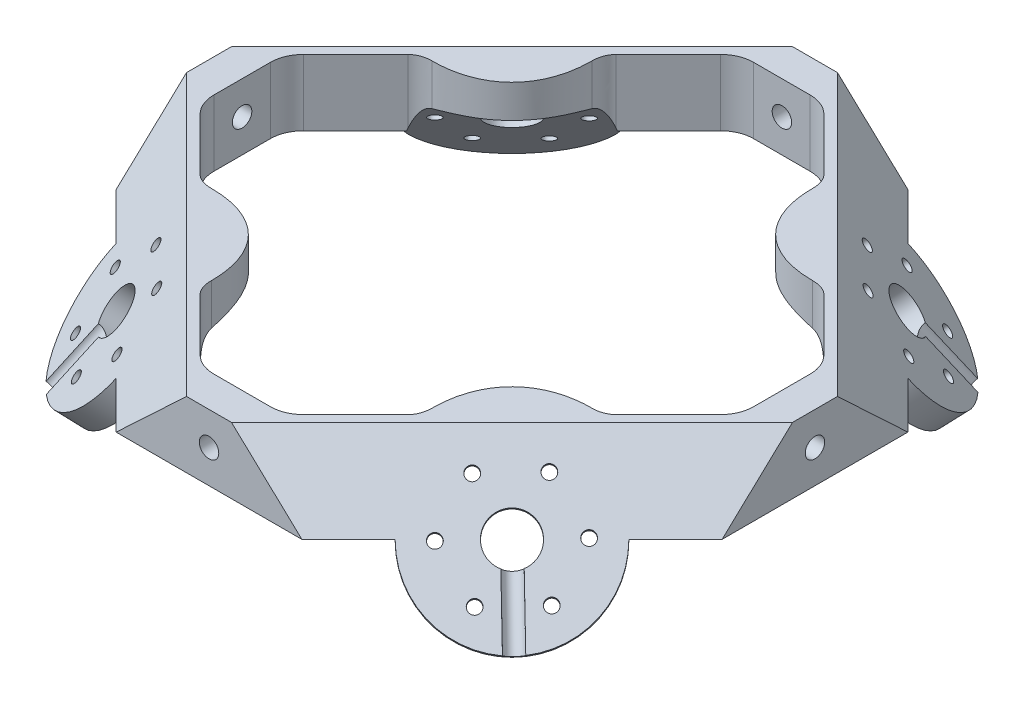
SolidWorks part; units mm, degrees
ref_plane "Front Plane" through (0, 0, 0) normal (0, 0, 1) x (1, 0, 0)
ref_plane "Top Plane" through (0, 0, 0) normal (0, 1, 0) x (1, 0, 0)
ref_plane "Right Plane" through (0, 0, 0) normal (1, 0, 0) x (0, 0, -1)
sketch "Sketch2" plane through (0, 0, 0) normal (0, 1, 0) x (1, 0, 0)
  line L1 (-45.825, -45.825) -> (45.825, -45.825)
  line L2 (-45.825, -45.825) -> (-45.825, 45.825)
  line L3 (-45.825, 45.825) -> (45.825, 45.825)
  line L4 (45.825, -45.825) -> (45.825, 45.825)
  line L5 (-45.825, -45.825) -> (45.825, 45.825) construction
  line L6 (-45.825, 45.825) -> (45.825, -45.825) construction
  circle A0 centre (0, 0) radius 3.175
  point P0 (0, 0)
  dimension "D2" = 6.35
  dimension "D1" = 91.65
extrude "Boss-Extrude2" add sketch "Sketch2" along normal blind 10
sketch "Sketch22" plane through (0, 10, 0) normal (0, 1, 0) x (1, 0, 0)
  circle A0 centre (0, 0) radius 3.9133
ref_axis "Axis4" through (0, 10, 0) along (0, 1, 0)
sketch "Sketch3" plane through (0, 10, 0) normal (0, 1, 0) x (1, 0, 0)
  line L0 (-45.825, -3.3986) -> (-3.3986, -45.825)
  line L1 (-45.825, 45.825) -> (-45.825, -45.825) construction
  line L2 (-45.825, -45.825) -> (45.825, -45.825) construction
  dimension "D1" = 45
  dimension "D2" = 30
ref_plane "Plane1" through (-19.0964, 20.3508, 19.0964) normal (-0.5647, 0.6018, 0.5647) x (0.7071, 0, 0.7071)
sketch "Sketch4" plane through (-19.0964, 20.3508, 19.0964) normal (-0.5647, 0.6018, 0.5647) x (0.7071, 0, 0.7071)
  line L0 (-30, -12.9606) -> (30, -12.9606) construction
  line L1 (30, -12.9606) -> (-30, -12.9606)
  line L2 (30, -12.9606) -> (30, -39.0014)
  line L3 (30, -39.0014) -> (-30, -39.0014)
  line L4 (-30, -12.9606) -> (-30, -39.0014)
extrude "Cut-Extrude1" cut sketch "Sketch4" along normal through all
sketch "Sketch5" plane through (-19.0964, 20.3508, 19.0964) normal (-0.5647, 0.6018, 0.5647) x (0.8253, 0.4118, 0.3864)
  line L3 (-32.3872, -10.2496) -> (6.1082, -33.4167) construction
  circle A0 centre (-13.1395, -21.8331) radius 12.5
  dimension "D1" = 25
extrude "Cut-Extrude2" cut sketch "Sketch5" against normal up to next from offset 4 offset against normal yes
sketch "Sketch6" plane through (-16.8376, 17.9436, 16.8376) normal (0.5647, -0.6018, -0.5647) x (0.8253, 0.4118, 0.3864)
  circle A0 centre (-13.1395, 21.8331) radius 12.5
  arc A1 (-21.9793, 12.9952) -> (-1.1912, 25.5058) centre (-13.1395, 21.8331) ccw construction
extrude "Boss-Extrude3" add sketch "Sketch6" against normal up to surface (4 mm away) up to face at (-27.276, 5, 27.276)
sketch "Sketch7" plane through (-16.8376, 17.9436, 16.8376) normal (0.5647, -0.6018, -0.5647) x (0.8253, 0.4118, 0.3864)
  line L1 (-13.1395, 13.5831) -> (-5.9948, 17.7081) construction
  line L2 (-5.9948, 17.7081) -> (-5.9948, 25.9581) construction
  line L3 (-5.9948, 25.9581) -> (-13.1395, 30.0831) construction
  line L4 (-13.1395, 30.0831) -> (-20.2842, 25.9581) construction
  line L5 (-20.2842, 25.9581) -> (-20.2842, 17.7081) construction
  line L6 (-20.2842, 17.7081) -> (-13.1395, 13.5831) construction
  circle A0 centre (-13.1395, 21.8331) radius 7.1447 construction
  circle A2 centre (-13.1395, 30.0831) radius 0.9
  circle A3 centre (-20.2842, 25.9581) radius 0.9
  circle A4 centre (-20.2842, 17.7081) radius 0.9
  circle A5 centre (-13.1395, 13.5831) radius 0.9
  circle A6 centre (-5.9948, 17.7081) radius 0.9
  circle A7 centre (-5.9948, 25.9581) radius 0.9
  circle A8 centre (-13.1395, 21.8331) radius 3.375
  arc A9 (-21.9793, 12.9952) -> (-1.1912, 25.5058) centre (-13.1395, 21.8331) ccw construction
  dimension "D2" = 1.8
  dimension "D3" = 6.75
  dimension "D1" = 16.5
extrude "Cut-Extrude3" cut sketch "Sketch7" against normal through all
ref_axis "Axis2" through (-29.4641, -6.1526, 35.4802) along (0.5647, -0.6018, -0.5647)
ref_axis "Axis3" through (-35.3605, -6.2723, 29.7113) along (0.5647, -0.6018, -0.5647)
ref_plane "Plane2" through (-13.4614, -26.0492, 14.2989) normal (-0.4126, -0.7985, 0.4383) x (0.2193, 0.3799, 0.8986)
sketch "Sketch17" plane through (-13.4614, -26.0492, 14.2989) normal (-0.4126, -0.7985, 0.4383) x (0.2193, 0.3799, 0.8986)
  line L0 (30.2204, 19.367) -> (10.456, 34.6728) construction
  circle A0 centre (20.3382, 27.0199) radius 1.25
  dimension "D1" = 2.5
extrude "Cut-Extrude8" cut sketch "Sketch17" against normal up to next and the other way through all
pattern_circular "CirPattern3" count 4 over 360 about axis through (0, 10, 0) along (0, 1, 0) of "Cut-Extrude8", "Cut-Extrude3", "Boss-Extrude3", "Cut-Extrude2", "Cut-Extrude1"
sketch "Sketch18" plane through (0, 0, 0) normal (0, -1, 0) x (1, 0, 0)
  line L0 (-14.0555, -45.825) -> (-21.1014, -38.7791) construction
  line L1 (-13.7845, -33.3905) -> (-6.35, -40.825)
  line L2 (-40.825, -6.35) -> (-40.825, 6.35)
  line L3 (-6.35, 40.825) -> (6.35, 40.825)
  line L4 (40.825, -6.35) -> (33.3905, -13.7845)
  line L5 (40.825, 6.35) -> (33.3905, 13.7845)
  line L6 (-45.825, -14.0555) -> (-45.825, 14.0555) construction
  line L7 (-6.35, -40.825) -> (6.35, -40.825)
  line L8 (13.7845, 33.3905) -> (6.35, 40.825)
  line L9 (-13.7845, 33.3905) -> (-6.35, 40.825)
  line L11 (40.825, -6.35) -> (40.825, 6.35)
  line L12 (14.0555, -45.825) -> (-14.0555, -45.825) construction
  line L13 (13.7845, -33.3905) -> (6.35, -40.825)
  line L14 (0, 0) -> (0, -40.825) construction
  line L20 (-40.825, 6.35) -> (-33.3905, 13.7845)
  line L21 (-40.825, -6.35) -> (-33.3905, -13.7845)
  line L22 (40.825, 0) -> (-40.825, 0) construction
  spline S0 degree 3 poles (651.7831, 1840.4478) (-301.2202, -130.8658) (-38.05, -89.2162) (-11.3299, -28.2857) (-10.7128, -26.1815) (-10.3137, -23.1157) (-10.2685, -22.1086) (-10.3687, -20.1466) (-10.5143, -19.1914) (-11.0109, -17.3644) (-11.3626, -16.4925) (-12.274, -14.8783) (-12.8342, -14.1368) (-14.1368, -12.8342) (-14.8783, -12.274) (-16.4925, -11.3626) (-17.3644, -11.0109) (-19.1914, -10.5143) (-20.1466, -10.3687) (-22.1086, -10.2685) (-23.1157, -10.3137) (-26.1815, -10.7128) (-28.2857, -11.3299) (-89.2167, -38.0502) (-130.8665, -301.225) (1840.5017, 651.8091) knots -3.40686 -3.40686 -3.40686 -3.40686 0.125 0.125 0.25 0.25 0.3125 0.3125 0.375 0.375 0.4375 0.4375 0.5 0.5 0.5625 0.5625 0.625 0.625 0.6875 0.6875 0.75 0.75 0.875 0.875 4.406893 4.406893 4.406893 4.406893 only from (-15.8109, -36.4636) to (-36.4636, -15.8109)
  spline S1 degree 3 poles (-13.7845, -33.3905) (-13.205, -32.3951) (-12.6888, -31.3843) (-11.3299, -28.2857) (-10.7128, -26.1815) (-10.3137, -23.1157) (-10.2685, -22.1086) (-10.3687, -20.1466) (-10.5143, -19.1914) (-11.0109, -17.3644) (-11.3626, -16.4925) (-12.274, -14.8783) (-12.8342, -14.1368) (-14.1368, -12.8342) (-14.8783, -12.274) (-16.4925, -11.3626) (-17.3644, -11.0109) (-19.1914, -10.5143) (-20.1466, -10.3687) (-22.1086, -10.2685) (-23.1157, -10.3137) (-26.1815, -10.7128) (-28.2857, -11.3299) (-31.3843, -12.6888) (-32.3951, -13.205) (-33.3905, -13.7845) knots 0.064029 0.064029 0.064029 0.064029 0.125 0.125 0.25 0.25 0.3125 0.3125 0.375 0.375 0.4375 0.4375 0.5 0.5 0.5625 0.5625 0.625 0.625 0.6875 0.6875 0.75 0.75 0.875 0.875 0.935971 0.935971 0.935971 0.935971
  spline S2 degree 3 poles (1840.4478, -651.7831) (-130.8658, 301.2202) (-89.2162, 38.05) (-28.2857, 11.3299) (-26.1815, 10.7128) (-23.1157, 10.3137) (-22.1086, 10.2685) (-20.1466, 10.3687) (-19.1914, 10.5143) (-17.3644, 11.0109) (-16.4925, 11.3626) (-14.8783, 12.274) (-14.1368, 12.8342) (-12.8342, 14.1368) (-12.274, 14.8783) (-11.3626, 16.4925) (-11.0109, 17.3644) (-10.5143, 19.1914) (-10.3687, 20.1466) (-10.2685, 22.1086) (-10.3137, 23.1157) (-10.7128, 26.1815) (-11.3299, 28.2857) (-38.0502, 89.2167) (-301.225, 130.8665) (651.8091, -1840.5017) knots -3.40686 -3.40686 -3.40686 -3.40686 0.125 0.125 0.25 0.25 0.3125 0.3125 0.375 0.375 0.4375 0.4375 0.5 0.5 0.5625 0.5625 0.625 0.625 0.6875 0.6875 0.75 0.75 0.875 0.875 4.406893 4.406893 4.406893 4.406893 only from (-36.4636, 15.8109) to (-15.8109, 36.4636)
  spline S3 degree 3 poles (-33.3905, 13.7845) (-32.3951, 13.205) (-31.3843, 12.6888) (-28.2857, 11.3299) (-26.1815, 10.7128) (-23.1157, 10.3137) (-22.1086, 10.2685) (-20.1466, 10.3687) (-19.1914, 10.5143) (-17.3644, 11.0109) (-16.4925, 11.3626) (-14.8783, 12.274) (-14.1368, 12.8342) (-12.8342, 14.1368) (-12.274, 14.8783) (-11.3626, 16.4925) (-11.0109, 17.3644) (-10.5143, 19.1914) (-10.3687, 20.1466) (-10.2685, 22.1086) (-10.3137, 23.1157) (-10.7128, 26.1815) (-11.3299, 28.2857) (-12.6888, 31.3843) (-13.205, 32.3951) (-13.7845, 33.3905) knots 0.064029 0.064029 0.064029 0.064029 0.125 0.125 0.25 0.25 0.3125 0.3125 0.375 0.375 0.4375 0.4375 0.5 0.5 0.5625 0.5625 0.625 0.625 0.6875 0.6875 0.75 0.75 0.875 0.875 0.935971 0.935971 0.935971 0.935971
  spline S4 degree 3 poles (33.3905, 13.7845) (32.3951, 13.205) (31.3843, 12.6888) (28.2857, 11.3299) (26.1815, 10.7128) (23.1157, 10.3137) (22.1086, 10.2685) (20.1466, 10.3687) (19.1914, 10.5143) (17.3644, 11.0109) (16.4925, 11.3626) (14.8783, 12.274) (14.1368, 12.8342) (12.8342, 14.1368) (12.274, 14.8783) (11.3626, 16.4925) (11.0109, 17.3644) (10.5143, 19.1914) (10.3687, 20.1466) (10.2685, 22.1086) (10.3137, 23.1157) (10.7128, 26.1815) (11.3299, 28.2857) (12.6888, 31.3843) (13.205, 32.3951) (13.7845, 33.3905) knots 0.064029 0.064029 0.064029 0.064029 0.125 0.125 0.25 0.25 0.3125 0.3125 0.375 0.375 0.4375 0.4375 0.5 0.5 0.5625 0.5625 0.625 0.625 0.6875 0.6875 0.75 0.75 0.875 0.875 0.935971 0.935971 0.935971 0.935971
  spline S5 degree 3 poles (13.7845, -33.3905) (13.205, -32.3951) (12.6888, -31.3843) (11.3299, -28.2857) (10.7128, -26.1815) (10.3137, -23.1157) (10.2685, -22.1086) (10.3687, -20.1466) (10.5143, -19.1914) (11.0109, -17.3644) (11.3626, -16.4925) (12.274, -14.8783) (12.8342, -14.1368) (14.1368, -12.8342) (14.8783, -12.274) (16.4925, -11.3626) (17.3644, -11.0109) (19.1914, -10.5143) (20.1466, -10.3687) (22.1086, -10.2685) (23.1157, -10.3137) (26.1815, -10.7128) (28.2857, -11.3299) (31.3843, -12.6888) (32.3951, -13.205) (33.3905, -13.7845) knots 0.064029 0.064029 0.064029 0.064029 0.125 0.125 0.25 0.25 0.3125 0.3125 0.375 0.375 0.4375 0.4375 0.5 0.5 0.5625 0.5625 0.625 0.625 0.6875 0.6875 0.75 0.75 0.875 0.875 0.935971 0.935971 0.935971 0.935971
  point P27 (0, 40.825)
  dimension "D3" = 5
  dimension "D4" = 5
  dimension "D5" = 6.35
  dimension "D6" = 12.7
  dimension "D1" = 2.5
  dimension "D2" = 2.5
extrude "Cut-Extrude13" cut sketch "Sketch18" against normal through all
sketch "Sketch21" plane through (-19.0964, 20.3508, 19.0964) normal (-0.5647, 0.6018, 0.5647) x (0.7071, 0, 0.7071)
  line L1 (-13.8635, -12.0888) -> (-9.6371, -12.0888)
  line L2 (-13.8635, -12.0888) -> (-24.3775, -12.0888) construction
  line L3 (9.6371, -12.0888) -> (13.8635, -12.0888)
  line L4 (24.3775, -12.0888) -> (13.8635, -12.0888) construction
  line L5 (-13.8635, -12.0888) -> (-13.8635, 0)
  line L6 (-13.8635, 0) -> (13.8635, 0)
  line L7 (13.8635, 0) -> (13.8635, -12.0888)
  circle A0 centre (0, -25.482) radius 12.5
  circle A1 centre (0, -25.482) radius 16.5
  dimension "D1" = 4
extrude "Cut-Extrude14" cut sketch "Sketch21" against normal through all contours A1 L3 L7 L6 L5 L1 region at (-21.3865, 16.0529, 21.3865)
pattern_circular "CirPattern4" count 4 over 360 about axis through (0, 10, 0) along (0, 1, 0) of "Cut-Extrude14"
fillet "Fillet1" radius 5 16 edges at (6.35, 5, 40.825) (-6.35, 5, 40.825) (-40.825, 5, 6.35) (-40.825, 5, -6.35) (-6.35, 5, -40.825) (6.35, 5, -40.825) (40.825, 5, -6.35) (40.825, 5, 6.35)
fillet "Fillet2" radius 5 8 edges at (-27.2343, 6.6242, -13.6053) (-13.6053, 6.6242, -27.2343) (27.2343, 6.6242, -13.6053) (13.6053, 6.6242, -27.2343) (-27.2343, 6.6242, 13.6053) (-13.6053, 6.6242, 27.2343) (13.6053, 6.6242, 27.2343) (27.2343, 6.6242, 13.6053)
sketch "Sketch23" plane through (0, 10, 0) normal (0, 1, 0) x (1, 0, 0)
  line L0 (11.2191, 35.9559) -> (15.7153, 31.4597) construction
  line L1 (7.8145, 39.3605) -> (11.2191, 35.9559) construction
  line L2 (-4.2789, 40.825) -> (4.2789, 40.825) construction
  line L3 (-11.2191, 35.9559) -> (-7.8145, 39.3605) construction
  line L4 (-15.7153, 31.4597) -> (-11.2191, 35.9559) construction
  line L5 (-35.9559, 11.2191) -> (-31.4597, 15.7153) construction
  line L6 (-39.3605, 7.8145) -> (-35.9559, 11.2191) construction
  line L7 (-40.825, -4.2789) -> (-40.825, 4.2789) construction
  line L8 (-35.9559, -11.2191) -> (-39.3605, -7.8145) construction
  line L9 (-31.4597, -15.7153) -> (-35.9559, -11.2191) construction
  line L10 (-11.2191, -35.9559) -> (-15.7153, -31.4597) construction
  line L11 (-7.8145, -39.3605) -> (-11.2191, -35.9559) construction
  line L12 (4.2789, -40.825) -> (-4.2789, -40.825) construction
  line L13 (11.2191, -35.9559) -> (7.8145, -39.3605) construction
  line L14 (15.7153, -31.4597) -> (11.2191, -35.9559) construction
  line L15 (35.9559, -11.2191) -> (31.4597, -15.7153) construction
  line L16 (39.3605, -7.8145) -> (35.9559, -11.2191) construction
  line L17 (40.825, 4.2789) -> (40.825, -4.2789) construction
  line L18 (35.9559, 11.2191) -> (39.3605, 7.8145) construction
  line L19 (11.2191, 35.9559) -> (15.7153, 31.4597)
  line L20 (11.2191, -35.9559) -> (15.7153, -31.4597)
  line L21 (7.8145, -39.3605) -> (11.2191, -35.9559)
  line L22 (-4.2789, -40.825) -> (4.2789, -40.825)
  line L23 (-11.2191, -35.9559) -> (-7.8145, -39.3605)
  line L24 (-15.7153, -31.4597) -> (-11.2191, -35.9559)
  line L25 (-35.9559, -11.2191) -> (-31.4597, -15.7153)
  line L26 (-39.3605, -7.8145) -> (-35.9559, -11.2191)
  line L27 (-40.825, 4.2789) -> (-40.825, -4.2789)
  line L28 (-35.9559, 11.2191) -> (-39.3605, 7.8145)
  line L29 (-31.4597, 15.7153) -> (-35.9559, 11.2191)
  line L30 (-11.2191, 35.9559) -> (-15.7153, 31.4597)
  line L31 (-7.8145, 39.3605) -> (-11.2191, 35.9559)
  line L32 (4.2789, 40.825) -> (-4.2789, 40.825)
  line L33 (11.2191, 35.9559) -> (7.8145, 39.3605)
  line L34 (15.7153, 31.4597) -> (11.2191, 35.9559)
  line L35 (35.9559, 11.2191) -> (31.4597, 15.7153)
  line L36 (39.3605, 7.8145) -> (35.9559, 11.2191)
  line L37 (40.825, -4.2789) -> (40.825, 4.2789)
  line L38 (35.9559, -11.2191) -> (39.3605, -7.8145)
  line L39 (31.4597, -15.7153) -> (35.9559, -11.2191)
  line L40 (11.2191, -35.9559) -> (15.7153, -31.4597)
  line L41 (7.8145, -39.3605) -> (11.2191, -35.9559)
  line L42 (-4.2789, -40.825) -> (4.2789, -40.825)
  line L43 (-11.2191, -35.9559) -> (-7.8145, -39.3605)
  line L44 (-15.7153, -31.4597) -> (-11.2191, -35.9559)
  line L45 (-35.9559, -11.2191) -> (-31.4597, -15.7153)
  line L46 (-39.3605, -7.8145) -> (-35.9559, -11.2191)
  line L47 (-40.825, 4.2789) -> (-40.825, -4.2789)
  line L48 (-35.9559, 11.2191) -> (-39.3605, 7.8145)
  line L49 (-31.4597, 15.7153) -> (-35.9559, 11.2191)
  line L50 (-11.2191, 35.9559) -> (-15.7153, 31.4597)
  line L51 (-7.8145, 39.3605) -> (-11.2191, 35.9559)
  line L52 (4.2789, 40.825) -> (-4.2789, 40.825)
  line L53 (11.2191, 35.9559) -> (7.8145, 39.3605)
  line L54 (15.7153, 31.4597) -> (11.2191, 35.9559)
  line L55 (35.9559, 11.2191) -> (31.4597, 15.7153)
  line L56 (39.3605, 7.8145) -> (35.9559, 11.2191)
  line L57 (40.825, -4.2789) -> (40.825, 4.2789)
  line L58 (35.9559, -11.2191) -> (39.3605, -7.8145)
  line L59 (31.4597, -15.7153) -> (35.9559, -11.2191)
  line L60 (7.8145, 39.3605) -> (11.2191, 35.9559)
  line L61 (-4.2789, 40.825) -> (4.2789, 40.825)
  line L62 (-11.2191, 35.9559) -> (-7.8145, 39.3605)
  line L63 (-15.7153, 31.4597) -> (-11.2191, 35.9559)
  line L64 (-35.9559, 11.2191) -> (-31.4597, 15.7153)
  line L65 (-39.3605, 7.8145) -> (-35.9559, 11.2191)
  line L66 (-40.825, -4.2789) -> (-40.825, 4.2789)
  line L67 (-35.9559, -11.2191) -> (-39.3605, -7.8145)
  line L68 (-31.4597, -15.7153) -> (-35.9559, -11.2191)
  line L69 (-11.2191, -35.9559) -> (-15.7153, -31.4597)
  line L70 (-7.8145, -39.3605) -> (-11.2191, -35.9559)
  line L71 (4.2789, -40.825) -> (-4.2789, -40.825)
  line L72 (11.2191, -35.9559) -> (7.8145, -39.3605)
  line L73 (15.7153, -31.4597) -> (11.2191, -35.9559)
  line L74 (35.9559, -11.2191) -> (31.4597, -15.7153)
  line L75 (39.3605, -7.8145) -> (35.9559, -11.2191)
  line L76 (40.825, 4.2789) -> (40.825, -4.2789)
  line L77 (35.9559, 11.2191) -> (39.3605, 7.8145)
  arc A0 (7.8145, 39.3605) -> (4.2789, 40.825) centre (4.2789, 35.825) ccw construction
  arc A1 (-4.2789, 40.825) -> (-7.8145, 39.3605) centre (-4.2789, 35.825) ccw construction
  arc A2 (-39.3605, 7.8145) -> (-40.825, 4.2789) centre (-35.825, 4.2789) ccw construction
  arc A3 (-40.825, -4.2789) -> (-39.3605, -7.8145) centre (-35.825, -4.2789) ccw construction
  arc A4 (-7.8145, -39.3605) -> (-4.2789, -40.825) centre (-4.2789, -35.825) ccw construction
  arc A5 (4.2789, -40.825) -> (7.8145, -39.3605) centre (4.2789, -35.825) ccw construction
  arc A6 (39.3605, -7.8145) -> (40.825, -4.2789) centre (35.825, -4.2789) ccw construction
  arc A7 (40.825, 4.2789) -> (39.3605, 7.8145) centre (35.825, 4.2789) ccw construction
  arc A8 (4.2789, -40.825) -> (7.8145, -39.3605) centre (4.2789, -35.825) ccw
  arc A9 (-7.8145, -39.3605) -> (-4.2789, -40.825) centre (-4.2789, -35.825) ccw
  arc A10 (-40.825, -4.2789) -> (-39.3605, -7.8145) centre (-35.825, -4.2789) ccw
  arc A11 (-39.3605, 7.8145) -> (-40.825, 4.2789) centre (-35.825, 4.2789) ccw
  arc A12 (-4.2789, 40.825) -> (-7.8145, 39.3605) centre (-4.2789, 35.825) ccw
  arc A13 (7.8145, 39.3605) -> (4.2789, 40.825) centre (4.2789, 35.825) ccw
  arc A14 (40.825, 4.2789) -> (39.3605, 7.8145) centre (35.825, 4.2789) ccw
  arc A15 (39.3605, -7.8145) -> (40.825, -4.2789) centre (35.825, -4.2789) ccw
  arc A16 (4.2789, -40.825) -> (7.8145, -39.3605) centre (4.2789, -35.825) ccw
  arc A17 (-7.8145, -39.3605) -> (-4.2789, -40.825) centre (-4.2789, -35.825) ccw
  arc A18 (-40.825, -4.2789) -> (-39.3605, -7.8145) centre (-35.825, -4.2789) ccw
  arc A19 (-39.3605, 7.8145) -> (-40.825, 4.2789) centre (-35.825, 4.2789) ccw
  arc A20 (-4.2789, 40.825) -> (-7.8145, 39.3605) centre (-4.2789, 35.825) ccw
  arc A21 (7.8145, 39.3605) -> (4.2789, 40.825) centre (4.2789, 35.825) ccw
  arc A22 (40.825, 4.2789) -> (39.3605, 7.8145) centre (35.825, 4.2789) ccw
  arc A23 (39.3605, -7.8145) -> (40.825, -4.2789) centre (35.825, -4.2789) ccw
  arc A24 (7.8145, 39.3605) -> (4.2789, 40.825) centre (4.2789, 35.825) ccw
  arc A25 (-4.2789, 40.825) -> (-7.8145, 39.3605) centre (-4.2789, 35.825) ccw
  arc A26 (-39.3605, 7.8145) -> (-40.825, 4.2789) centre (-35.825, 4.2789) ccw
  arc A27 (-40.825, -4.2789) -> (-39.3605, -7.8145) centre (-35.825, -4.2789) ccw
  arc A28 (-7.8145, -39.3605) -> (-4.2789, -40.825) centre (-4.2789, -35.825) ccw
  arc A29 (4.2789, -40.825) -> (7.8145, -39.3605) centre (4.2789, -35.825) ccw
  arc A30 (39.3605, -7.8145) -> (40.825, -4.2789) centre (35.825, -4.2789) ccw
  arc A31 (40.825, 4.2789) -> (39.3605, 7.8145) centre (35.825, 4.2789) ccw
  ellipse E0 centre (9.8405, 25.5849) end of major axis (15.7153, 31.4597) minor radius 5 (16.6971, 28.78) -> (15.7153, 31.4597) ccw construction
  ellipse E1 centre (-9.8405, 25.5849) end of major axis (-15.7153, 31.4597) minor radius 5 (-15.7153, 31.4597) -> (-16.6971, 28.78) ccw construction
  ellipse E2 centre (-39.3239, 39.3239) end of major axis (-58.7106, 58.7106) minor radius 16.5 (-28.78, 16.6971) -> (-16.6971, 28.78) ccw construction
  ellipse E3 centre (-25.5849, 9.8405) end of major axis (-31.4597, 15.7153) minor radius 5 (-28.78, 16.6971) -> (-31.4597, 15.7153) ccw construction
  ellipse E4 centre (-25.5849, -9.8405) end of major axis (-19.7101, -3.9657) minor radius 5 (-31.4597, -15.7153) -> (-28.78, -16.6971) ccw construction
  ellipse E5 centre (-39.3239, -39.3239) end of major axis (-58.7106, -58.7106) minor radius 16.5 (-16.6971, -28.78) -> (-28.78, -16.6971) ccw construction
  ellipse E6 centre (-9.8405, -25.5849) end of major axis (-15.7153, -31.4597) minor radius 5 (-16.6971, -28.78) -> (-15.7153, -31.4597) ccw construction
  ellipse E7 centre (9.8405, -25.5849) end of major axis (3.9657, -19.7101) minor radius 5 (15.7153, -31.4597) -> (16.6971, -28.78) ccw construction
  ellipse E8 centre (39.3239, -39.3239) end of major axis (58.7106, -58.7106) minor radius 16.5 (28.78, -16.6971) -> (16.6971, -28.78) ccw construction
  ellipse E9 centre (25.5849, -9.8405) end of major axis (31.4597, -15.7153) minor radius 5 (28.78, -16.6971) -> (31.4597, -15.7153) ccw construction
  ellipse E10 centre (9.8405, 25.5849) end of major axis (15.7153, 31.4597) minor radius 5 (16.6971, 28.78) -> (15.7153, 31.4597) ccw
  ellipse E11 centre (-9.8405, 25.5849) end of major axis (-15.7153, 31.4597) minor radius 5 (-15.7153, 31.4597) -> (-16.6971, 28.78) ccw
  ellipse E12 centre (39.3239, -39.3239) end of major axis (58.7106, -58.7106) minor radius 16.5 (28.78, -16.6971) -> (16.6971, -28.78) ccw
  ellipse E13 centre (9.8405, -25.5849) end of major axis (15.7153, -31.4597) minor radius 5 (15.7153, -31.4597) -> (16.6971, -28.78) ccw
  ellipse E14 centre (-9.8405, -25.5849) end of major axis (-3.9657, -19.7101) minor radius 5 (-16.6971, -28.78) -> (-15.7153, -31.4597) ccw
  ellipse E15 centre (-39.3239, -39.3239) end of major axis (-58.7106, -58.7106) minor radius 16.5 (-16.6971, -28.78) -> (-28.78, -16.6971) ccw
  ellipse E16 centre (-25.5849, -9.8405) end of major axis (-31.4597, -15.7153) minor radius 5 (-31.4597, -15.7153) -> (-28.78, -16.6971) ccw
  ellipse E17 centre (-25.5849, 9.8405) end of major axis (-31.4597, 15.7153) minor radius 5 (-28.78, 16.6971) -> (-31.4597, 15.7153) ccw
  ellipse E18 centre (-39.3239, 39.3239) end of major axis (-58.7106, 58.7106) minor radius 16.5 (-28.78, 16.6971) -> (-16.6971, 28.78) ccw
  ellipse E19 centre (-9.8405, 25.5849) end of major axis (-15.7153, 31.4597) minor radius 5 (-15.7153, 31.4597) -> (-16.6971, 28.78) ccw
  ellipse E20 centre (9.8405, 25.5849) end of major axis (15.7153, 31.4597) minor radius 5 (16.6971, 28.78) -> (15.7153, 31.4597) ccw
  ellipse E21 centre (39.3239, 39.3239) end of major axis (58.7106, 58.7106) minor radius 16.5 (16.6971, 28.78) -> (28.78, 16.6971) ccw
  ellipse E22 centre (25.5849, 9.8405) end of major axis (31.4597, 15.7153) minor radius 5 (31.4597, 15.7153) -> (28.78, 16.6971) ccw
  ellipse E23 centre (25.5849, -9.8405) end of major axis (31.4597, -15.7153) minor radius 5 (28.78, -16.6971) -> (31.4597, -15.7153) ccw
  ellipse E24 centre (39.3239, -39.3239) end of major axis (58.7106, -58.7106) minor radius 16.5 (28.78, -16.6971) -> (16.6971, -28.78) ccw
  ellipse E25 centre (9.8405, -25.5849) end of major axis (15.7153, -31.4597) minor radius 5 (15.7153, -31.4597) -> (16.6971, -28.78) ccw
  ellipse E26 centre (-9.8405, -25.5849) end of major axis (-15.7153, -31.4597) minor radius 5 (-16.6971, -28.78) -> (-15.7153, -31.4597) ccw
  ellipse E27 centre (-39.3239, -39.3239) end of major axis (-58.7106, -58.7106) minor radius 16.5 (-16.6971, -28.78) -> (-28.78, -16.6971) ccw
  ellipse E28 centre (-25.5849, -9.8405) end of major axis (-19.7101, -3.9657) minor radius 5 (-31.4597, -15.7153) -> (-28.78, -16.6971) ccw
  ellipse E29 centre (-25.5849, 9.8405) end of major axis (-31.4597, 15.7153) minor radius 5 (-28.78, 16.6971) -> (-31.4597, 15.7153) ccw
  ellipse E30 centre (-39.3239, 39.3239) end of major axis (-58.7106, 58.7106) minor radius 16.5 (-28.78, 16.6971) -> (-16.6971, 28.78) ccw
  ellipse E31 centre (-9.8405, 25.5849) end of major axis (-15.7153, 31.4597) minor radius 5 (-15.7153, 31.4597) -> (-16.6971, 28.78) ccw
  ellipse E32 centre (9.8405, 25.5849) end of major axis (15.7153, 31.4597) minor radius 5 (16.6971, 28.78) -> (15.7153, 31.4597) ccw
  ellipse E33 centre (39.3239, 39.3239) end of major axis (58.7106, 58.7106) minor radius 16.5 (16.6971, 28.78) -> (28.78, 16.6971) ccw
  ellipse E34 centre (25.5849, 9.8405) end of major axis (31.4597, 15.7153) minor radius 5 (31.4597, 15.7153) -> (28.78, 16.6971) ccw
  ellipse E35 centre (25.5849, -9.8405) end of major axis (31.4597, -15.7153) minor radius 5 (28.78, -16.6971) -> (31.4597, -15.7153) ccw
  ellipse E36 centre (-39.3239, 39.3239) end of major axis (-58.7106, 58.7106) minor radius 16.5 (-28.78, 16.6971) -> (-16.6971, 28.78) ccw
  ellipse E37 centre (-25.5849, 9.8405) end of major axis (-31.4597, 15.7153) minor radius 5 (-28.78, 16.6971) -> (-31.4597, 15.7153) ccw
  ellipse E38 centre (-25.5849, -9.8405) end of major axis (-31.4597, -15.7153) minor radius 5 (-31.4597, -15.7153) -> (-28.78, -16.6971) ccw
  ellipse E39 centre (-39.3239, -39.3239) end of major axis (-58.7106, -58.7106) minor radius 16.5 (-16.6971, -28.78) -> (-28.78, -16.6971) ccw
  ellipse E40 centre (-9.8405, -25.5849) end of major axis (-15.7153, -31.4597) minor radius 5 (-16.6971, -28.78) -> (-15.7153, -31.4597) ccw
  ellipse E41 centre (9.8405, -25.5849) end of major axis (15.7153, -31.4597) minor radius 5 (15.7153, -31.4597) -> (16.6971, -28.78) ccw
  ellipse E42 centre (39.3239, -39.3239) end of major axis (58.7106, -58.7106) minor radius 16.5 (28.78, -16.6971) -> (16.6971, -28.78) ccw
  ellipse E43 centre (25.5849, -9.8405) end of major axis (31.4597, -15.7153) minor radius 5 (28.78, -16.6971) -> (31.4597, -15.7153) ccw
  ellipse M41 centre (39.3239, -39.3239) end of major axis (58.7106, -58.7106) minor radius 16.5 (28.78, -16.6971) -> (16.6971, -28.78) ccw
  ellipse M42 centre (9.8405, -25.5849) end of major axis (15.7153, -31.4597) minor radius 5 (16.6971, -28.78) -> (15.7153, -31.4597) cw
  line M43 (15.7153, -31.4597) -> (11.2191, -35.9559)
  line M44 (11.2191, -35.9559) -> (7.8145, -39.3605)
  arc M45 (7.8145, -39.3605) -> (4.2789, -40.825) centre (4.2789, -35.825) cw
  line M46 (4.2789, -40.825) -> (-4.2789, -40.825)
  arc M47 (-4.2789, -40.825) -> (-7.8145, -39.3605) centre (-4.2789, -35.825) cw
  line M48 (-7.8145, -39.3605) -> (-11.2191, -35.9559)
  line M49 (-11.2191, -35.9559) -> (-15.7153, -31.4597)
  ellipse M50 centre (-9.8405, -25.5849) end of major axis (-15.7153, -31.4597) minor radius 5 (-15.7153, -31.4597) -> (-16.6971, -28.78) cw
  ellipse M51 centre (-39.3239, -39.3239) end of major axis (-58.7106, -58.7106) minor radius 16.5 (-16.6971, -28.78) -> (-28.78, -16.6971) ccw
  ellipse M52 centre (-25.5849, -9.8405) end of major axis (-31.4597, -15.7153) minor radius 5 (-28.78, -16.6971) -> (-31.4597, -15.7153) cw
  line M53 (-31.4597, -15.7153) -> (-35.9559, -11.2191)
  line M54 (-35.9559, -11.2191) -> (-39.3605, -7.8145)
  arc M55 (-39.3605, -7.8145) -> (-40.825, -4.2789) centre (-35.825, -4.2789) cw
  line M56 (-40.825, -4.2789) -> (-40.825, 4.2789)
  arc M57 (-40.825, 4.2789) -> (-39.3605, 7.8145) centre (-35.825, 4.2789) cw
  line M58 (-39.3605, 7.8145) -> (-35.9559, 11.2191)
  line M59 (-35.9559, 11.2191) -> (-31.4597, 15.7153)
  ellipse M60 centre (-25.5849, 9.8405) end of major axis (-31.4597, 15.7153) minor radius 5 (-31.4597, 15.7153) -> (-28.78, 16.6971) cw
  ellipse M61 centre (-39.3239, 39.3239) end of major axis (-58.7106, 58.7106) minor radius 16.5 (-28.78, 16.6971) -> (-16.6971, 28.78) ccw
  ellipse M62 centre (-9.8405, 25.5849) end of major axis (-15.7153, 31.4597) minor radius 5 (-16.6971, 28.78) -> (-15.7153, 31.4597) cw
  line M63 (-15.7153, 31.4597) -> (-11.2191, 35.9559)
  line M64 (-11.2191, 35.9559) -> (-7.8145, 39.3605)
  arc M65 (-7.8145, 39.3605) -> (-4.2789, 40.825) centre (-4.2789, 35.825) cw
  line M66 (-4.2789, 40.825) -> (4.2789, 40.825)
  arc M67 (4.2789, 40.825) -> (7.8145, 39.3605) centre (4.2789, 35.825) cw
  line M68 (7.8145, 39.3605) -> (11.2191, 35.9559)
  line M69 (11.2191, 35.9559) -> (15.7153, 31.4597)
  ellipse M70 centre (9.8405, 25.5849) end of major axis (15.7153, 31.4597) minor radius 5 (15.7153, 31.4597) -> (16.6971, 28.78) cw
  ellipse M71 centre (39.3239, 39.3239) end of major axis (58.7106, 58.7106) minor radius 16.5 (16.6971, 28.78) -> (28.78, 16.6971) ccw
  ellipse M72 centre (25.5849, 9.8405) end of major axis (31.4597, 15.7153) minor radius 5 (28.78, 16.6971) -> (31.4597, 15.7153) cw
  line M73 (31.4597, 15.7153) -> (35.9559, 11.2191)
  line M74 (35.9559, 11.2191) -> (39.3605, 7.8145)
  arc M75 (39.3605, 7.8145) -> (40.825, 4.2789) centre (35.825, 4.2789) cw
  line M76 (40.825, 4.2789) -> (40.825, -4.2789)
  arc M77 (40.825, -4.2789) -> (39.3605, -7.8145) centre (35.825, -4.2789) cw
  line M78 (39.3605, -7.8145) -> (35.9559, -11.2191)
  line M79 (35.9559, -11.2191) -> (31.4597, -15.7153)
  ellipse M80 centre (25.5849, -9.8405) end of major axis (31.4597, -15.7153) minor radius 5 (31.4597, -15.7153) -> (28.78, -16.6971) cw
  dimension "D1" = 0
extrude "Cut-Extrude15" cut sketch "Sketch23" against normal through all contours M41 M80 M79 M78 M77 M76 M75 M74 M73 M72 M71 M70 M69 M68 M67 M66 M65 M64 M63 M62 M61 M60 M59 M58 M57 M56 M55 M54 M53 M52 M51 M50 M49 M48 M47 M46 M45 M44 M43 M42 region at (0, 10, 0)
hole_wizard "#4 Clearance Hole1" positions "3DSketch1" profile "Sketch24" hole size "#4" standard "ANSI Inch" end condition through all
sketch3d "3DSketch1"
  line L4 (45.825, 10, 0) -> (45.825, 0, 0) construction
  line L5 (45.825, 10, 3.3986) -> (45.825, 10, -3.3986) construction
  line L6 (45.825, 0, 14.0555) -> (45.825, 0, -14.0555) construction
  point P0 (0, 5, 45.825)
  point P2 (45.825, 5, 0)
sketch "Sketch24" plane through (0, 5, 45.825) normal (1, 0, 0) x (0, -1, 0)
  line L0 (0, 0) -> (0, 91.65)
  line L1 (0, 91.65) -> (1.4732, 91.65)
  line L2 (1.4732, 91.65) -> (1.4732, 0)
  line L5 (1.4732, 0) -> (0, 0)
  line L11 (0, -6.35) -> (0, 107.95) construction
  dimension "Thru Hole Dia." = 2.9464
  dimension "Thru Hole Depth" = 91.65
